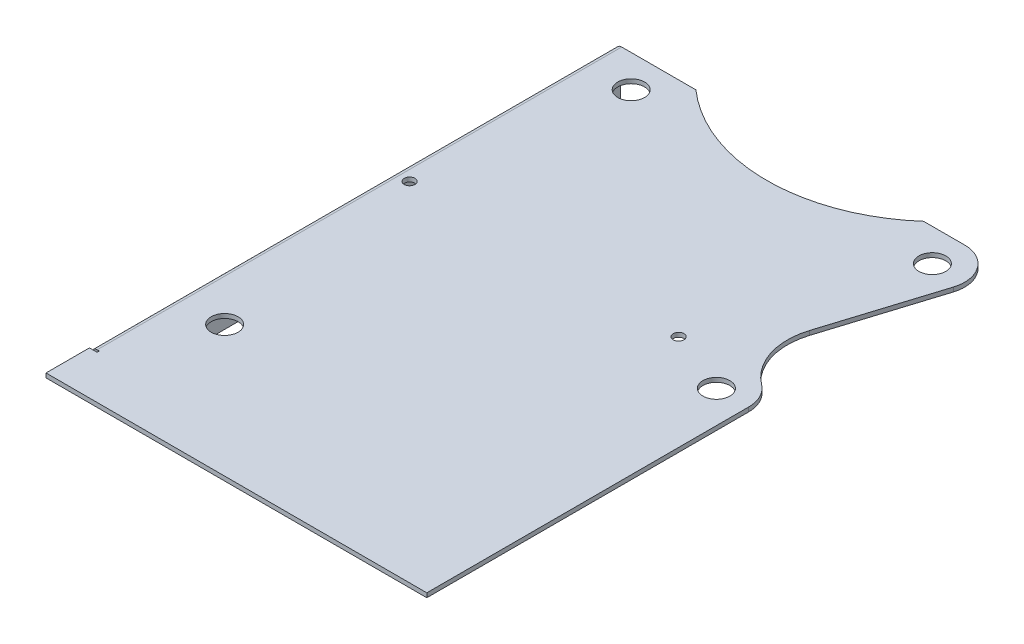
SolidWorks part; units mm, degrees
note: The reader was unsure of these and kept them because the rebuilt part matched: flange length of "Edge-Flange2".
material "PC High Viscosity"
ref_plane "Front Plane" through (0, 0, 0) normal (0, 0, 1) x (1, 0, 0)
ref_plane "Top Plane" through (0, 0, 0) normal (0, 1, 0) x (1, 0, 0)
ref_plane "Right Plane" through (0, 0, 0) normal (1, 0, 0) x (0, 0, -1)
sketch "Sketch1" plane through (0, 0, 0) normal (0, 1, 0) x (1, 0, 0)
  line L0 (109.6195, 311.8073) -> (89.362, 247.1155)
  line L1 (110.49, 0) -> (-114.3, 0)
  line L3 (91.44, 336.55) -> (67.2021, 336.55)
  line L4 (-114.3, 0) -> (-114.3, 336.55)
  line L5 (110.49, 190.0033) -> (110.49, 0)
  line L6 (0, 311.15) -> (0, 336.55) construction
  line L7 (-67.2021, 336.55) -> (-114.3, 336.55)
  line L8 (47.5267, 137.5363) -> (47.5267, 226.8471) construction
  line L9 (-98.5505, 265.4761) -> (-98.5505, 137.5363) construction
  arc A0 (109.6195, 311.8073) -> (91.44, 336.55) centre (91.44, 317.5) ccw
  circle A1 centre (91.44, 317.5) radius 7.6886 construction
  arc A2 (110.49, 190.0033) -> (102.867, 205.2456) centre (91.44, 190.0033) ccw
  circle A3 centre (91.44, 190.0033) radius 7.9375 construction
  arc A4 (89.362, 247.1155) -> (102.867, 205.2456) centre (125.721, 235.73) ccw
  arc A5 (-67.2021, 336.55) -> (67.2021, 336.55) centre (0, 412.75) ccw
  circle A7 centre (-86.36, 317.5) radius 7.9375
  circle A8 centre (91.44, 317.5) radius 7.9375
  circle A9 centre (91.44, 190.0033) radius 7.9375
  circle A10 centre (-86.36, 77.5033) radius 7.9375
  circle A11 centre (-104.9005, 205.2456) radius 3.175
  circle A12 centre (53.8767, 205.2456) radius 3.175
  point P0 (0, 0)
  dimension "D1" = 38.1
  dimension "D3" = 76.2
  dimension "D4" = 25.4
  dimension "D5" = 101.6
  dimension "D6" = 6.35
  dimension "D7" = 6.35
  dimension "D2" = 114.3
base flange "Base-Flange1" sketch "Sketch1" thickness 2.54 reverse thickness direction no parameters "D1"=0.7366
edge flange "Edge-Flange1" [suppressed] sketch "Sketch4" flange angle 90 flange position material inside bend radius 0.7366 thickness 2.54
sketch "Sketch4" plane through (-114.3, 0, 0) normal (1, 0, 0) x (0, 0, -1)
  line L0 (25.3365, 0) -> (25.3365, 12.6238) construction
  line L2 (25.3365, 0) -> (25.3365, 22.86)
  line L3 (25.3365, 22.86) -> (336.55, 22.86)
  line L4 (336.55, 22.86) -> (336.55, 0)
  line L5 (336.55, 0) -> (0, 0) construction
  line L6 (336.55, 0) -> (25.3365, 0)
bend "EdgeBend2" bend radius 0.7366 bend angle 90 parameters "D5"=1, "D6"=10, "D7"=25.4
edge flange "Edge-Flange2" sketch "Sketch9" flange angle 90 flange length 27.94 flange position material inside bend radius 0.7366 thickness 2.54 relief rectangular parameters "D6"=10
sketch "Sketch9" plane through (-114.3, -2.54, 0) normal (1, 0, 0) x (0, 0, 1)
  line L2 (-336.55, 0) -> (-336.55, 25.4)
  line L3 (-336.55, 25.4) -> (-26.924, 25.4)
  line L4 (-26.924, 25.4) -> (-26.924, 0)
  line L5 (0, 0) -> (-336.55, 0) construction
  line L6 (-26.924, 0) -> (-336.55, 0)
  line L7 (-25.3365, 12.6238) -> (-25.3365, 10.6299) construction
  dimension "D1" = 1.5875
  dimension "D2" = 25.4
bend "EdgeBend3" bend radius 0.7366 bend angle 90 parameters "D5"=1
sketch "Bend-Lines1" [suppressed] plane through (0, 0, 0) normal (0, 1, 0) x (1, 0, 0)
sketch "Bounding-Box1" [suppressed] plane through (0, 0, 0) normal (0, 1, 0) x (1, 0, 0)
sheet metal parameters "Sheet-Metal1" thickness 2.54 parameters "D1"=0.7366
flat pattern "Flat-Pattern1" [suppressed]
sketch "Bend-Lines2" plane through (0, 0, 0) normal (0, 1, 0) x (1, 0, 0)
sketch3d "Bounding-Box2" [suppressed]
  line L0 (-204.0394, 19.05, 0) -> (-204.0394, -317.5, 0) construction
  line L1 (19.05, 19.05, 0) -> (19.05, -317.5, 0) construction
  line L2 (-204.0394, 19.05, 0) -> (19.05, 19.05, 0) construction
  line L3 (-204.0394, -317.5, 0) -> (19.05, -317.5, 0) construction
sheet metal parameters "Sheet-Metal2" [suppressed] thickness 2.54 parameters "D1"=0.7366
flat pattern "Flat-Pattern1"
sketch "Bend-Lines2" plane through (0, 0, 0) normal (0, 1, 0) x (1, 0, 0)
sketch3d "Bounding-Box2" [suppressed]
  line L0 (-226.0381, 19.05, 0) -> (-226.0381, -317.5, 0) construction
  line L1 (19.05, 19.05, 0) -> (19.05, -317.5, 0) construction
  line L2 (-226.0381, 19.05, 0) -> (19.05, 19.05, 0) construction
  line L3 (-226.0381, -317.5, 0) -> (19.05, -317.5, 0) construction
bend of the flat pattern "Flatten-<EdgeBend2>1"
sheet metal parameters "Sheet-Metal3" [suppressed] thickness 2.54 parameters "D1"=0.7366
flat pattern "Flat-Pattern1"
sketch "Bend-Lines2" plane through (0, 0, 0) normal (0, 1, 0) x (1, 0, 0)
  line L0 (-112.5994, 336.55) -> (-112.5994, 26.924) construction
  line L1 (-112.5994, 336.55) -> (-112.5994, 26.924) construction
sketch3d "Bounding-Box2" [suppressed]
  line L0 (-230.2788, 146.5467, 0) -> (-230.2788, -190.0033, 0) construction
  line L1 (19.05, 146.5467, 0) -> (19.05, -190.0033, 0) construction
  line L2 (-230.2788, 146.5467, 0) -> (19.05, 146.5467, 0) construction
  line L3 (-230.2788, -190.0033, 0) -> (19.05, -190.0033, 0) construction
bend of the flat pattern "Flatten-<EdgeBend3>1"
